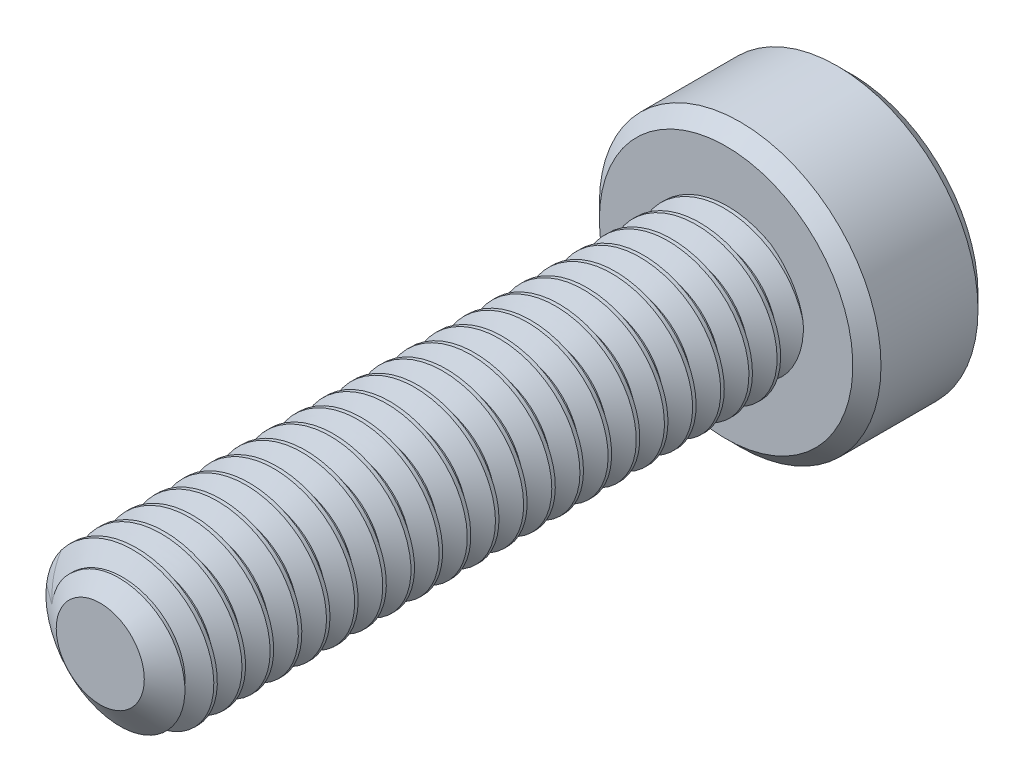
SolidWorks part; units mm, degrees
other "DetailItem1"
ref_plane "Front Plane" through (0, 0, 0) normal (0, 0, 1) x (1, 0, 0)
ref_plane "Top Plane" through (0, 0, 0) normal (0, 1, 0) x (1, 0, 0)
ref_plane "Right Plane" through (0, 0, 0) normal (1, 0, 0) x (0, 0, -1)
sketch "Sketch1" plane through (0, 0, 0) normal (0, 0, 1) x (1, 0, 0)
  circle A0 centre (0, 0) radius 1.25
  dimension "OD" = 2.5
extrude "Extrude1" add sketch "Sketch1" against normal blind 10
sketch "Sketch2" plane through (0, 0, 0) normal (0, 0, 1) x (1, 0, 0)
  circle A0 centre (0, 0) radius 1.25 construction
  circle A1 centre (0, 0) radius 1.25
curve "Helix/Spiral1" pitch 0.45 height 10.45 radius 1.25 centre (0, 0, 0) axis (0, 0, -1) start towards (0, 1, 0) parameters "pitch"=0.45
sketch "Sketch3" plane through (0, 0, 0) normal (1, 0, 0) x (0, 0, -1)
  line L0 (-0.3937, 1.25) -> (-0.225, 0.9577)
  line L1 (-0.225, 0.9577) -> (-0.1687, 0.9577)
  line L2 (-0.1687, 0.9577) -> (0, 1.25)
  line L3 (-0.3937, 1.25) -> (0, 1.25)
  line L4 (-0.1969, 1.25) -> (-0.1969, 0.9577) construction
  line L5 (-0.3094, 1.1039) -> (-0.0844, 1.1039) construction
  line L6 (0, 1.25) -> (0, -1.25) construction
  dimension "D1" = 0.0563
  dimension "D2" = 0.225
  dimension "D3" = 60
sweep "Cut-Sweep1" cut profiles "Sketch3" path "Helix/Spiral1" align with end faces yes
sketch "Sketch4" plane through (0, 0, 0) normal (1, 0, 0) x (0, 0, -1)
  line L0 (0.3825, 1.25) -> (0, 0.7037)
  line L1 (0, 0.7037) -> (0, 1.25)
  line L2 (0.3825, 1.25) -> (0, 1.25)
  line L3 (-0.3937, 1.25) -> (0, 1.25) construction
  line L4 (0, 0) -> (7.0209, 0) construction
  dimension "D1" = 55
  dimension "D2" = 0.254
revolve "Cut-Revolve1" cut sketch "Sketch4" angle 360 about L4
sketch "Sketch6" plane through (0, 0, -10) normal (0, 0, -1) x (-1, 0, 0)
  circle A0 centre (0, 0) radius 2.25
  dimension "head dia" = 4.5
extrude "Extrude2" add sketch "Sketch6" along normal blind 2
sketch "Sketch7" plane through (0, 0, -12) normal (0, 0, -1) x (-1, 0, 0)
  line L1 (0, 0.866) -> (-0.75, 0.433)
  line L2 (-0.75, 0.433) -> (-0.75, -0.433)
  line L3 (-0.75, -0.433) -> (0, -0.866)
  line L4 (0, -0.866) -> (0.75, -0.433)
  line L5 (0.75, -0.433) -> (0.75, 0.433)
  line L6 (0.75, 0.433) -> (0, 0.866)
  circle A0 centre (0, 0) radius 0.75 construction
  dimension "hex dia" = 1.5
extrude "Cut-Extrude1" cut sketch "Sketch7" against normal blind 1.125
sketch "Sketch8" plane through (0, 0, -12) normal (0, 0, -1) x (-1, 0, 0)
  circle A0 centre (0, 0) radius 0.866
extrude "Cut-Extrude2" cut sketch "Sketch8" against normal through all draft 45
chamfer "Chamfer1" distance 0.225 angle 45 2 edges at (-2.25, 0, -12) (-2.25, 0, -10)
sketch "Sketch10" plane through (0, 0, -10) normal (0, 0, 1) x (1, 0, 0)
  circle A1 centre (0, 0) radius 1.25
  circle A2 centre (0, 0) radius 1.25
  dimension "D1" = 0
ref_plane "Plane1" through (0, 0, -30) normal (0, 0, 1) x (1, 0, 0)
extrude "partial thread" [suppressed] add sketch "Sketch10" along normal up to surface (10 mm away) separate body
chamfer "Chamfer2" [suppressed] distance 0.05 angle 45
combine bodies "Combine1" [suppressed] operation type add bodies to combine 107 108
sketch "Sketch9" plane through (0, 0, 0) normal (1, 0, 0) x (0, 0, -1)
  line L0 (0, 1.25) -> (0, -1.25) construction
  line L1 (1.125, 1.25) -> (1.125, -1.25) construction
  dimension "D1" = 1.125
equation "\"D3@Helix/Spiral1\" = \"screw length@Extrude1\"+\"pitch@Helix/Spiral1\""
equation "\"D1@Sketch3\" = \"pitch@Helix/Spiral1\"*.125"
equation "\"D2@Sketch3\" = \"pitch@Helix/Spiral1\"*.5"
equation "\"D1@Cut-Extrude1\" = \"hex dia@Sketch7\"*.75"
equation "\"D1@Chamfer1\" = \"head dia@Sketch6\"*.05"
equation "\"D1@Sketch9\" = \"pitch@Helix/Spiral1\"*2.5"
equation "\"D1@Chamfer2\"=\"OD@Sketch1\"*.02"
